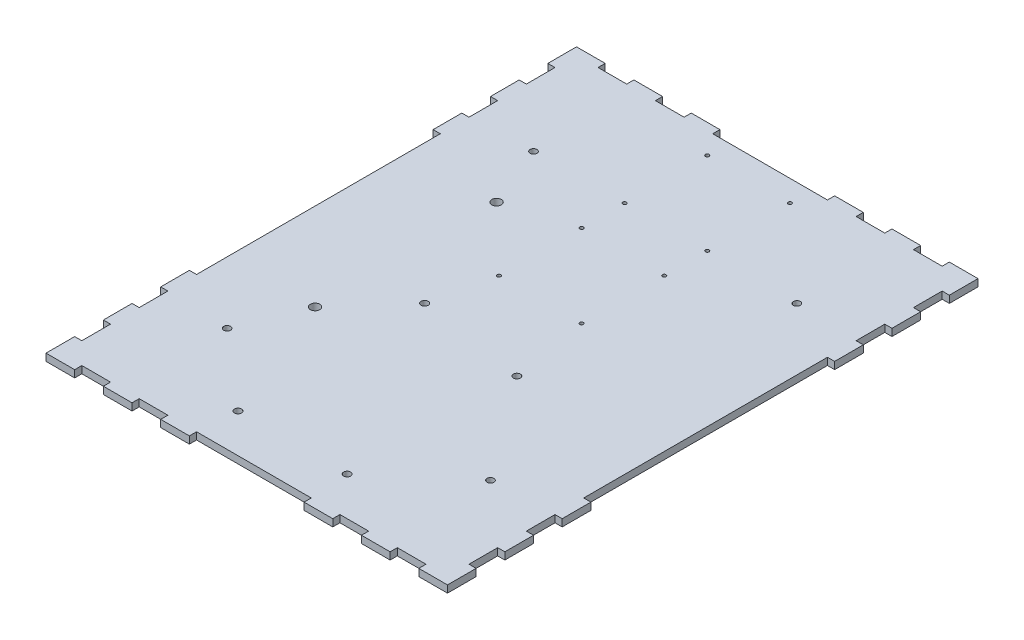
SolidWorks part; units mm, degrees
material "Acrylic (Medium-high impact)"
ref_plane "Front Plane" through (0, 0, 0) normal (0, 0, 1) x (1, 0, 0)
ref_plane "Top Plane" through (0, 0, 0) normal (0, 1, 0) x (1, 0, 0)
ref_plane "Right Plane" through (0, 0, 0) normal (1, 0, 0) x (0, 0, -1)
sketch "Sketch1" plane through (0, 0, 0) normal (0, 1, 0) x (1, 0, 0)
  line L0 (0, 209.55) -> (0, 196.85)
  line L1 (0, 0) -> (177.8, 0)
  line L2 (0, 0) -> (0, 234.95)
  line L3 (0, 234.95) -> (177.8, 234.95)
  line L4 (177.8, 0) -> (177.8, 234.95)
  line L5 (0, 234.95) -> (3.175, 234.95)
  line L6 (0, 234.95) -> (0, 0)
  line L7 (0, 0) -> (3.175, 0)
  line L8 (3.175, 234.95) -> (3.175, 0)
  line L9 (177.8, 234.95) -> (174.625, 234.95)
  line L10 (177.8, 234.95) -> (177.8, 0)
  line L11 (177.8, 0) -> (174.625, 0)
  line L12 (174.625, 234.95) -> (174.625, 0)
  line L13 (0, 234.95) -> (3.175, 234.95)
  line L14 (0, 234.95) -> (0, 222.25)
  line L15 (0, 222.25) -> (3.175, 222.25)
  line L16 (3.175, 234.95) -> (3.175, 222.25)
  line L17 (0, 209.55) -> (3.175, 209.55)
  line L18 (3.175, 209.55) -> (3.175, 196.85)
  line L19 (0, 196.85) -> (3.175, 196.85)
  line L20 (0, 184.15) -> (0, 171.45)
  line L21 (0, 184.15) -> (3.175, 184.15)
  line L22 (3.175, 184.15) -> (3.175, 171.45)
  line L23 (0, 171.45) -> (3.175, 171.45)
  line L24 (0, 117.475) -> (177.8, 117.475) construction
  line L25 (88.9, 234.95) -> (88.9, 0) construction
  line L26 (177.8, 171.45) -> (174.625, 171.45)
  line L27 (174.625, 184.15) -> (174.625, 171.45)
  line L28 (177.8, 184.15) -> (174.625, 184.15)
  line L29 (177.8, 184.15) -> (177.8, 171.45)
  line L30 (177.8, 196.85) -> (174.625, 196.85)
  line L31 (174.625, 209.55) -> (174.625, 196.85)
  line L32 (177.8, 209.55) -> (174.625, 209.55)
  line L33 (174.625, 234.95) -> (174.625, 222.25)
  line L34 (177.8, 222.25) -> (174.625, 222.25)
  line L35 (177.8, 234.95) -> (177.8, 222.25)
  line L36 (177.8, 234.95) -> (174.625, 234.95)
  line L37 (177.8, 234.95) -> (177.8, 0)
  line L38 (177.8, 234.95) -> (174.625, 234.95)
  line L39 (177.8, 209.55) -> (177.8, 196.85)
  line L40 (177.8, 25.4) -> (177.8, 38.1)
  line L41 (177.8, 0) -> (174.625, 0)
  line L42 (177.8, 0) -> (174.625, 0)
  line L43 (177.8, 0) -> (177.8, 12.7)
  line L44 (177.8, 12.7) -> (174.625, 12.7)
  line L45 (174.625, 0) -> (174.625, 12.7)
  line L46 (177.8, 25.4) -> (174.625, 25.4)
  line L47 (174.625, 25.4) -> (174.625, 38.1)
  line L48 (177.8, 38.1) -> (174.625, 38.1)
  line L49 (177.8, 50.8) -> (177.8, 63.5)
  line L50 (177.8, 50.8) -> (174.625, 50.8)
  line L51 (174.625, 50.8) -> (174.625, 63.5)
  line L52 (177.8, 63.5) -> (174.625, 63.5)
  line L53 (0, 63.5) -> (3.175, 63.5)
  line L54 (3.175, 50.8) -> (3.175, 63.5)
  line L55 (0, 50.8) -> (3.175, 50.8)
  line L56 (0, 50.8) -> (0, 63.5)
  line L57 (0, 38.1) -> (3.175, 38.1)
  line L58 (3.175, 25.4) -> (3.175, 38.1)
  line L59 (0, 25.4) -> (3.175, 25.4)
  line L60 (3.175, 0) -> (3.175, 12.7)
  line L61 (0, 12.7) -> (3.175, 12.7)
  line L62 (0, 0) -> (0, 12.7)
  line L63 (0, 0) -> (3.175, 0)
  line L64 (177.8, 0) -> (174.625, 0)
  line L65 (0, 0) -> (3.175, 0)
  line L66 (0, 0) -> (177.8, 0)
  line L67 (0, 25.4) -> (0, 38.1)
  dimension "D1" = 234.95
  dimension "D2" = 177.8
  dimension "D3" = 3.175
  dimension "D4" = 3.175
  dimension "D5" = 12.7
  dimension "D6" = 3.175
  dimension "D7" = 3
extrude "Boss-Extrude1" add sketch "Sketch1" along normal blind 3.175 contours L6 L55 L8 L53 | L6 L59 L8 L57 | L61 L2 L1 L8 | L6 L23 L8 L21 | L0 L19 L8 L17 | L6 L15 L8 L3 | L4 L44 L12 L1 | L37 L48 L12 L46 | L37 L52 L12 L50 | L34 L10 L3 L12 | L10 L32 L12 L30 | L10 L28 L12 L26 | L52 L12 L26 L27 L28 L30 L31 L32 L34 L33 L3 L8 L1 L45 L44 L46 L47 L48 L50 L51 region at (1.5875, 0, -203.2) region at (1.5875, 0, -228.6) region at (88.9, 0, -117.475) region at (1.5875, 0, -177.8) region at (1.5875, 0, -57.15) region at (176.2125, 0, -228.6) region at (1.5875, 0, -31.75) region at (176.2125, 0, -203.2) region at (1.5875, 0, -6.35) region at (176.2125, 0, -177.8) region at (176.2125, 0, -57.15) region at (176.2125, 0, -6.35) region at (176.2125, 0, -31.75)
sketch "Sketch2" plane through (0, 3.175, 0) normal (0, 1, 0) x (1, 0, 0)
  line L0 (3.175, 12.7) -> (30.5816, 12.7)
  line L1 (30.5816, 0) -> (30.5816, 234.95)
  line L3 (0, 0) -> (177.8, 0) construction
  line L4 (0, 234.95) -> (177.8, 234.95) construction
  line L5 (30.5816, 0) -> (30.5816, 14.0716)
  line L6 (30.5816, 14.0716) -> (30.5816, 49.6316)
  line L7 (3.175, 117.475) -> (174.625, 117.475) construction
  line L8 (3.175, 171.45) -> (3.175, 63.5) construction
  line L9 (174.625, 171.45) -> (174.625, 63.5) construction
  line L10 (88.9, 234.95) -> (88.9, 0) construction
  circle A0 centre (30.5816, 49.6316) radius 1.524
  circle A1 centre (147.2184, 49.6316) radius 1.524
  circle A2 centre (147.2184, 185.3184) radius 1.524
  circle A3 centre (30.5816, 185.3184) radius 1.524
  dimension "D4" = 3.048
  dimension "D1" = 27.4066
  dimension "D2" = 14.0716
  dimension "D3" = 35.56
extrude "Cut-Extrude1" cut sketch "Sketch2" against normal blind 3.175 and the other way through all contours A3 L1 | A3 L1 | L1 A0 L6 | L6 A0 L1 | A1 | A2 region at (29.9348, 3.175, -49.6316) region at (29.9348, 3.175, -185.3184) region at (31.2284, 3.175, -185.3184) region at (31.2284, 3.175, -49.6316) region at (147.2184, 3.175, -49.6316) region at (147.2184, 3.175, -185.3184)
sketch "Sketch3" plane through (0, 3.175, 0) normal (0, 1, 0) x (1, 0, 0)
  line L0 (88.9, 234.95) -> (88.9, 0) construction
  line L1 (0, 234.95) -> (177.8, 234.95) construction
  line L2 (0, 0) -> (177.8, 0) construction
  line L4 (88.9, 234.95) -> (70.6, 234.95)
  line L5 (88.9, 234.95) -> (88.9, 222.25)
  line L6 (88.9, 222.25) -> (70.6, 222.25)
  line L7 (70.6, 234.95) -> (70.6, 222.25)
  line L8 (70.6, 222.25) -> (107.2, 222.25)
  line L9 (70.6, 222.25) -> (70.6, 185.65)
  line L10 (70.6, 185.65) -> (107.2, 185.65)
  line L11 (107.2, 222.25) -> (107.2, 185.65)
  line L12 (70.6, 166.6) -> (107.2, 166.6)
  line L13 (70.6, 166.6) -> (70.6, 130)
  line L14 (70.6, 130) -> (107.2, 130)
  line L15 (107.2, 166.6) -> (107.2, 130)
  circle A0 centre (70.6, 222.25) radius 0.8
  circle A1 centre (107.2, 222.25) radius 0.8
  circle A2 centre (70.6, 185.65) radius 0.8
  circle A3 centre (107.2, 185.65) radius 0.8
  circle A4 centre (70.6, 166.6) radius 0.8
  circle A5 centre (107.2, 166.6) radius 0.8
  circle A6 centre (70.6, 130) radius 0.8
  circle A7 centre (107.2, 130) radius 0.8
  dimension "D4" = 1.6
  dimension "D5" = 1.6
  dimension "D6" = 1.6
  dimension "D7" = 1.6
  dimension "D8" = 36.6
  dimension "D10" = 1.6
  dimension "D11" = 1.6
  dimension "D12" = 1.6
  dimension "D13" = 1.6
  dimension "D1" = 12.7
  dimension "D2" = 18.3
  dimension "D3" = 36.6
  dimension "D9" = 19.05
extrude "Cut-Extrude2" cut sketch "Sketch3" against normal blind 5.715 contours L8 A0 L7 | L7 A0 L9 | L9 A0 L8 | L8 A1 L11 | L11 A1 L8 | L10 A2 L9 | L9 A2 L10 | L11 A3 L10 | L10 A3 L11 | L13 A4 L12 | L12 A4 L13 | L12 A5 L15 | L15 A5 L12 | L14 A6 L13 | L13 A6 L14 | L15 A7 L14 | L14 A7 L15 region at (70.9395, 3.175, -222.5895) region at (70.2605, 3.175, -222.25) region at (70.9395, 3.175, -221.9105) region at (107.3132, 3.175, -222.3632) region at (106.8605, 3.175, -221.9105) region at (70.9395, 3.175, -185.9895) region at (70.4868, 3.175, -185.5368) region at (107.3132, 3.175, -185.5368) region at (106.8605, 3.175, -185.9895) region at (70.4868, 3.175, -166.7132) region at (70.9395, 3.175, -166.2605) region at (107.3132, 3.175, -166.7132) region at (106.8605, 3.175, -166.2605) region at (70.9395, 3.175, -130.3395) region at (70.4868, 3.175, -129.8868) region at (107.3132, 3.175, -129.8868) region at (106.8605, 3.175, -130.3395)
sketch "Sketch4" plane through (0, 3.175, 0) normal (0, 1, 0) x (1, 0, 0)
  line L0 (88.9, 0) -> (88.9, 20.32) construction
  line L1 (0, 0) -> (177.8, 0) construction
  line L2 (88.9, 20.32) -> (64.7319, 20.32) construction
  line L3 (64.7319, 20.32) -> (64.7319, 95.4532) construction
  line L4 (64.7319, 20.32) -> (113.0681, 20.32) construction
  line L5 (113.0681, 20.32) -> (113.0681, 102.9462) construction
  circle A0 centre (64.7319, 20.32) radius 1.5621
  circle A3 centre (113.0681, 20.32) radius 1.5621
  circle A4 centre (64.7319, 102.9462) radius 1.5621
  circle A5 centre (113.0681, 95.4532) radius 1.5621
  dimension "D3" = 3.1242
  dimension "D4" = 75.1332
  dimension "D9" = 3.1242
  dimension "D1" = 20.32
  dimension "D2" = 24.1681
  dimension "D6" = 48.3362
  dimension "D7" = 82.6262
extrude "Cut-Extrude3" cut sketch "Sketch4" against normal blind 10.16 contours A3 | A0 | A4 | A5 region at (64.7319, 3.175, -20.32) region at (113.0681, 3.175, -20.32) region at (64.7319, 3.175, -102.9462) region at (113.0681, 3.175, -95.4532)
sketch "Sketch5" plane through (0, 3.175, 0) normal (0, 1, 0) x (1, 0, 0)
  line L0 (88.9, 0) -> (88.9, 18.3402) construction
  line L1 (0, 0) -> (177.8, 0) construction
  line L3 (0, 0) -> (12.7, 0)
  line L4 (0, 0) -> (0, 3.175)
  line L5 (0, 3.175) -> (12.7, 3.175)
  line L6 (12.7, 0) -> (12.7, 3.175)
  line L10 (25.4, 3.175) -> (38.1, 3.175)
  line L11 (25.4, 0) -> (38.1, 0)
  line L12 (38.1, 0) -> (38.1, 3.175)
  line L13 (25.4, 0) -> (25.4, 3.175)
  line L14 (50.8, 3.175) -> (63.5, 3.175)
  line L15 (50.8, 0) -> (63.5, 0)
  line L16 (63.5, 0) -> (63.5, 3.175)
  line L17 (50.8, 0) -> (50.8, 3.175)
  line L18 (0, 3.175) -> (177.8, 3.175)
  line L19 (127, 0) -> (127, 3.175)
  line L20 (114.3, 0) -> (114.3, 3.175)
  line L21 (127, 0) -> (114.3, 0)
  line L22 (127, 3.175) -> (114.3, 3.175)
  line L23 (152.4, 0) -> (152.4, 3.175)
  line L24 (139.7, 0) -> (139.7, 3.175)
  line L25 (152.4, 0) -> (139.7, 0)
  line L26 (152.4, 3.175) -> (139.7, 3.175)
  line L27 (165.1, 0) -> (165.1, 3.175)
  line L28 (177.8, 3.175) -> (165.1, 3.175)
  line L29 (177.8, 0) -> (177.8, 3.175)
  line L30 (177.8, 0) -> (165.1, 0)
  line L63 (0, 63.5) -> (0, 50.8)
  line L64 (0, 50.8) -> (3.175, 50.8)
  line L65 (3.175, 50.8) -> (3.175, 38.1)
  line L66 (3.175, 38.1) -> (0, 38.1)
  line L67 (0, 38.1) -> (0, 25.4)
  line L68 (0, 25.4) -> (3.175, 25.4)
  line L69 (3.175, 25.4) -> (3.175, 12.7)
  line L70 (3.175, 12.7) -> (0, 12.7)
  line L71 (0, 12.7) -> (0, 0)
  line L72 (0, 0) -> (177.8, 0)
  line L73 (177.8, 0) -> (177.8, 12.7)
  line L74 (177.8, 12.7) -> (174.625, 12.7)
  line L75 (174.625, 12.7) -> (174.625, 25.4)
  line L76 (174.625, 25.4) -> (177.8, 25.4)
  line L77 (177.8, 25.4) -> (177.8, 38.1)
  line L78 (177.8, 38.1) -> (174.625, 38.1)
  line L79 (174.625, 38.1) -> (174.625, 50.8)
  line L80 (174.625, 50.8) -> (177.8, 50.8)
  line L81 (177.8, 50.8) -> (177.8, 63.5)
  line L82 (177.8, 63.5) -> (174.625, 63.5)
  line L83 (174.625, 63.5) -> (174.625, 171.45)
  line L84 (174.625, 171.45) -> (177.8, 171.45)
  line L85 (177.8, 171.45) -> (177.8, 184.15)
  line L86 (177.8, 184.15) -> (174.625, 184.15)
  line L87 (174.625, 184.15) -> (174.625, 196.85)
  line L88 (174.625, 196.85) -> (177.8, 196.85)
  line L89 (177.8, 196.85) -> (177.8, 209.55)
  line L90 (177.8, 209.55) -> (174.625, 209.55)
  line L91 (174.625, 209.55) -> (174.625, 222.25)
  line L92 (174.625, 222.25) -> (177.8, 222.25)
  line L93 (177.8, 222.25) -> (177.8, 234.95)
  line L94 (177.8, 234.95) -> (0, 234.95)
  line L95 (0, 234.95) -> (0, 222.25)
  line L96 (0, 222.25) -> (3.175, 222.25)
  line L97 (3.175, 222.25) -> (3.175, 209.55)
  line L98 (3.175, 209.55) -> (0, 209.55)
  line L99 (0, 209.55) -> (0, 196.85)
  line L100 (0, 196.85) -> (3.175, 196.85)
  line L101 (3.175, 196.85) -> (3.175, 184.15)
  line L102 (3.175, 184.15) -> (0, 184.15)
  line L103 (0, 184.15) -> (0, 171.45)
  line L104 (0, 171.45) -> (3.175, 171.45)
  line L105 (3.175, 171.45) -> (3.175, 63.5)
  line L106 (3.175, 63.5) -> (0, 63.5)
  line L107 (0, 63.5) -> (0, 50.8)
  line L108 (0, 50.8) -> (3.175, 50.8)
  line L109 (3.175, 50.8) -> (3.175, 38.1)
  line L110 (3.175, 38.1) -> (0, 38.1)
  line L111 (0, 38.1) -> (0, 25.4)
  line L112 (0, 25.4) -> (3.175, 25.4)
  line L113 (3.175, 25.4) -> (3.175, 12.7)
  line L114 (3.175, 12.7) -> (0, 12.7)
  line L115 (0, 12.7) -> (0, 0)
  line L116 (0, 0) -> (177.8, 0)
  line L117 (177.8, 0) -> (177.8, 12.7)
  line L118 (177.8, 12.7) -> (174.625, 12.7)
  line L119 (174.625, 12.7) -> (174.625, 25.4)
  line L120 (174.625, 25.4) -> (177.8, 25.4)
  line L121 (177.8, 25.4) -> (177.8, 38.1)
  line L122 (177.8, 38.1) -> (174.625, 38.1)
  line L123 (174.625, 38.1) -> (174.625, 50.8)
  line L124 (174.625, 50.8) -> (177.8, 50.8)
  line L125 (177.8, 50.8) -> (177.8, 63.5)
  line L126 (177.8, 63.5) -> (174.625, 63.5)
  line L127 (174.625, 63.5) -> (174.625, 171.45)
  line L128 (174.625, 171.45) -> (177.8, 171.45)
  line L129 (177.8, 171.45) -> (177.8, 184.15)
  line L130 (177.8, 184.15) -> (174.625, 184.15)
  line L131 (174.625, 184.15) -> (174.625, 196.85)
  line L132 (174.625, 196.85) -> (177.8, 196.85)
  line L133 (177.8, 196.85) -> (177.8, 209.55)
  line L134 (177.8, 209.55) -> (174.625, 209.55)
  line L135 (174.625, 209.55) -> (174.625, 222.25)
  line L136 (174.625, 222.25) -> (177.8, 222.25)
  line L137 (177.8, 222.25) -> (177.8, 234.95)
  line L138 (177.8, 234.95) -> (0, 234.95)
  line L139 (0, 234.95) -> (0, 222.25)
  line L140 (0, 222.25) -> (3.175, 222.25)
  line L141 (3.175, 222.25) -> (3.175, 209.55)
  line L142 (3.175, 209.55) -> (0, 209.55)
  line L143 (0, 209.55) -> (0, 196.85)
  line L144 (0, 196.85) -> (3.175, 196.85)
  line L145 (3.175, 196.85) -> (3.175, 184.15)
  line L146 (3.175, 184.15) -> (0, 184.15)
  line L147 (0, 184.15) -> (0, 171.45)
  line L148 (0, 171.45) -> (3.175, 171.45)
  line L149 (3.175, 171.45) -> (3.175, 63.5)
  line L150 (3.175, 63.5) -> (0, 63.5)
  point P22 (88.9, 3.175)
  dimension "D1" = 3.175
  dimension "D2" = 12.7
  dimension "D4" = 0
  dimension "D3" = 3
extrude "Cut-Extrude4" cut sketch "Sketch5" against normal blind 7.62 contours L6 L116 L13 L18 | L12 L116 L17 L18 | L116 L0 L18 L16 | L0 L116 L20 L18 | L19 L116 L24 L18 | L23 L116 L27 L18 region at (76.2, 3.175, -1.5875) region at (101.6, 3.175, -1.5875) region at (44.45, 3.175, -1.5875) region at (133.35, 3.175, -1.5875) region at (19.05, 3.175, -1.5875) region at (158.75, 3.175, -1.5875)
ref_plane "Plane2" through (0, 0, -117.475) normal (0, 0, 1) x (1, 0, 0)
mirror "Mirror1" about plane through (0, 0, -117.475) normal (0, 0, 1) of "Cut-Extrude4"
sketch "Sketch7" plane through (0, 0, 0) normal (0, -1, 0) x (1, 0, 0)
  line L0 (3.175, -117.475) -> (41.8719, -117.475) construction
  line L1 (3.175, -171.45) -> (3.175, -63.5) construction
  line L2 (41.8719, -3.175) -> (41.8719, -231.775) construction
  line L3 (38.1, -3.175) -> (50.8, -3.175) construction
  line L4 (38.1, -231.775) -> (50.8, -231.775) construction
  circle A0 centre (64.7319, -102.9462) radius 1.5621 construction
  circle A1 centre (41.8719, -77.2795) radius 2.0955
  circle A2 centre (41.8719, -157.6705) radius 2.0955
  dimension "D2" = 4.191
  dimension "D1" = 22.86
  dimension "D3" = 40.1955
extrude "Cut-Extrude5" cut sketch "Sketch7" against normal blind 7.62
sketch "Sketch17" plane through (0, 3.175, 0) normal (0, 1, 0) x (1, 0, 0)
  line L0 (91.2081, 361.6852) -> (457.2081, 361.6852) construction
  line L1 (133.0743, 97.8218) -> (123.5696, 97.8218)
  line L2 (123.5696, 97.8218) -> (123.5696, 114.4551)
  line L3 (123.5696, 114.4551) -> (49.0171, 114.4551)
  line L4 (96.8376, 126.336) -> (96.8376, 114.4551)
  line L5 (41.4006, 69.0107) -> (41.4006, 10.2003)
  line L6 (41.4006, 10.2003) -> (58.8188, 10.2003)
  line L7 (96.8376, 182.0344) -> (96.8376, 173.9503)
  line L8 (96.8376, 173.9503) -> (41.7, 173.9503)
  line L9 (41.7, 173.9503) -> (41.7, 165.8662)
  line L10 (152.4827, 75.7429) -> (123.5696, 75.7429)
  line L11 (123.5696, 75.7429) -> (123.5696, 155.3867)
  line L12 (123.5696, 155.3867) -> (109.9661, 155.3867)
  line L13 (21.0405, 75.7429) -> (24.3341, 75.7429)
  line L14 (24.3341, 75.7429) -> (24.3341, 168.2615)
  line L15 (24.3341, 168.2615) -> (60.8624, 168.2615)
  line L16 (60.8624, 168.2615) -> (60.8624, 155.3867)
  line L17 (60.8624, 155.3867) -> (68.0483, 155.3867)
  line L18 (21.0405, 157.782) -> (24.3341, 157.782)
  line L19 (24.3341, 157.782) -> (24.3341, 168.2615)
  line L20 (60.8624, 168.2615) -> (60.8624, 211.3769)
  line L21 (60.8624, 211.3769) -> (68.0483, 211.3769)
  line L22 (109.9661, 211.3769) -> (123.5696, 211.3769)
  line L23 (155.0958, 157.782) -> (123.5696, 157.782)
  line L24 (123.5696, 157.782) -> (123.5696, 211.3769)
  line L25 (36.6766, 179.7822) -> (58.8188, 179.7822)
  line L26 (58.8188, 179.7822) -> (58.8188, 80.6555)
  line L27 (58.8188, 80.6555) -> (75.4402, 80.6555)
  line L28 (36.6766, 52.3642) -> (75.4402, 52.3642)
  line L29 (141.0042, 52.3642) -> (103.507, 52.3642)
  line L30 (141.0042, 179.7822) -> (120.7991, 179.7822)
  line L31 (120.7991, 179.7822) -> (120.7991, 80.6555)
  line L32 (120.7991, 80.6555) -> (103.507, 80.6555)
